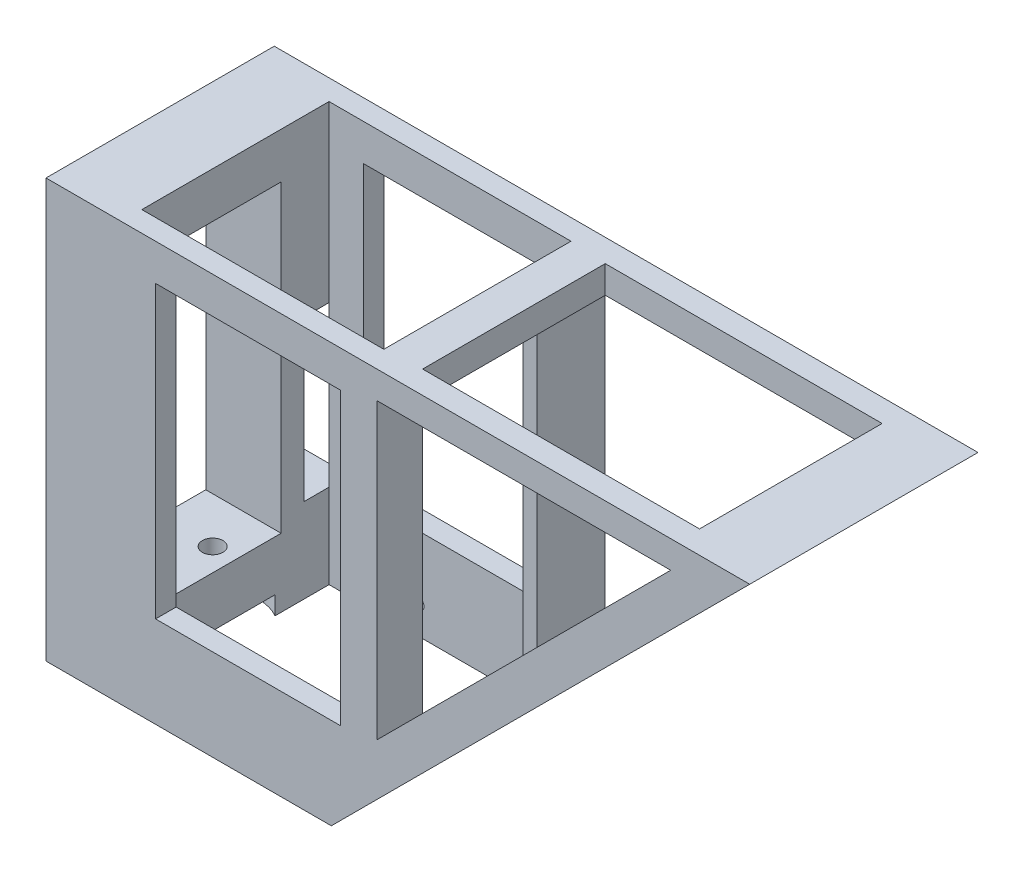
SolidWorks part; units mm, degrees
ref_plane "Plan de face" through (0, 0, 0) normal (0, 0, 1) x (1, 0, 0)
ref_plane "Plan de dessus" through (0, 0, 0) normal (0, 1, 0) x (1, 0, 0)
ref_plane "Plan de droite" through (0, 0, 0) normal (1, 0, 0) x (0, 0, -1)
sketch "Main-Sketch" plane through (0, 0, 0) normal (0, 0, 1) x (1, 0, 0)
  line L0 (0, 91.65) -> (154.15, 91.65)
  line L1 (154.15, 91.65) -> (62.5, 0)
  line L2 (62.5, 0) -> (0, 0)
  line L3 (0, 0) -> (0, 91.65)
  dimension "D1" = 62.5
  dimension "D2" = 154.15
  dimension "D3" = 135
extrude "Main-Extrusion" add sketch "Main-Sketch" along normal blind 50
ref_plane "Plan1" through (0, 0, 45) normal (0, 0, 1) x (1, 0, 0)
sketch "Fix-Bottom-Sheet-Sketch" plane through (0, 0, 0) normal (0, 0, -1) x (-1, 0, 0)
  line L0 (-62.5, 0) -> (-154.15, 91.65) construction
  circle A0 centre (-105.4994, 50.0705) radius 1.35
  circle A1 centre (-35.9453, 6.2286) radius 1.35
  dimension "D1" = 2.7
  dimension "D2" = 5
  dimension "D3" = 66
extrude "Fix-Bottom-Sheet-Extrusion" cut sketch "Fix-Bottom-Sheet-Sketch" against normal blind 10
sketch "Esquisse2" plane through (0, 0, 0) normal (0, -1, 0) x (-1, 0, 0)
  line L0 (0, -50) -> (0, 0) construction
  line L1 (-16.5, -45.5) -> (-69.5, -45.5)
  line L2 (-16.5, -45.5) -> (-16.5, -4.5)
  line L3 (-16.5, -4.5) -> (-69.5, -4.5)
  line L4 (-69.5, -45.5) -> (-69.5, -4.5)
  line L5 (0, -50) -> (-62.5, -50) construction
  point P4 (-16.5, -25)
  point P7 (0, -25)
  point P8 (0, 0)
  point P11 (-31.25, -50)
  point P12 (-69.5, -25)
  point P13 (-16.3275, -4.5)
  dimension "D1" = 41
  dimension "D2" = 16.5
  dimension "D3" = 53
extrude "Enlèv. mat.-Extru.2" cut sketch "Esquisse2" against normal through all
sketch "Esquisse3" plane through (0, 0, 50) normal (0, 0, 1) x (1, 0, 0)
  line L0 (72.5, 85.65) -> (72.5, 21.3137)
  line L1 (72.5, 21.3137) -> (136.8363, 85.65)
  line L2 (136.8363, 85.65) -> (72.5, 85.65)
  line L3 (62.5, 0) -> (154.15, 91.65) construction
  line L4 (154.15, 91.65) -> (0, 91.65) construction
  point P7 (76.6426, 83.65)
  dimension "D1" = 8
  dimension "D2" = 6
  dimension "D3" = 10
extrude "Enlèv. mat.-Extru.3" cut sketch "Esquisse3" against normal through all
sketch "Esquisse4" plane through (0, 0, 0) normal (0, 0, -1) x (-1, 0, 0)
  line L0 (0, 91.65) -> (0, 0) construction
  line L1 (0, 18.5) -> (-16.5, 18.5)
  line L2 (0, 18.5) -> (0, 53.5)
  line L3 (0, 53.5) -> (-16.5, 53.5)
  line L4 (-16.5, 18.5) -> (-16.5, 53.5)
  line L5 (0, 0) -> (-62.5, 0) construction
  dimension "D1" = 16.5
  dimension "D2" = 18.5
  dimension "D3" = 35
extrude "Enlèv. mat.-Extru.4" cut sketch "Esquisse4" against normal blind 10
sketch "Esquisse6" plane through (0, 0, 0) normal (0, -1, 0) x (1, 0, 0)
  line L0 (16.5, 45.5) -> (16.5, 4.5) construction
  line L1 (0, 50) -> (0, 0) construction
  circle A0 centre (11.5, 25) radius 10
  point P7 (0, 25)
  dimension "D1" = 20
  dimension "D2" = 5
extrude "Enlèv. mat.-Extru.6" cut sketch "Esquisse6" against normal blind 4
sketch "Esquisse7" plane through (0, 4, 0) normal (0, -1, 0) x (1, 0, 0)
  circle A0 centre (11.5, 25) radius 2.25
  circle A1 centre (11.5, 25) radius 10 construction
  dimension "D1" = 4.5
extrude "Enlèv. mat.-Extru.7" cut sketch "Esquisse7" against normal blind 15
ref_plane "Plan2" through (0, 15, 0) normal (0, -1, 0) x (1, 0, 0)
ref_plane "Plan3" through (0, 85.65, 0) normal (0, 1, 0) x (1, 0, 0)
sketch "Esquisse8" plane through (0, 85.65, 0) normal (0, 1, 0) x (-1, 0, 0)
  line L1 (-11.5, 40) -> (-5, 40)
  line L2 (-11.5, 40) -> (-11.5, 15)
  line L3 (-11.5, 15) -> (-5, 15)
  line L4 (-5, 40) -> (-5, 15)
  line L6 (-16.5, 45.5) -> (-16.5, 4.5) construction
  line L7 (0, 50) -> (0, 0) construction
  line L8 (-154.15, 0) -> (0, 0) construction
  line L9 (-154.15, 50) -> (0, 50) construction
  dimension "D1" = 5
  dimension "D2" = 5
  dimension "D3" = 15
  dimension "D4" = 10
extrude "Enlèv. mat.-Extru.8" cut sketch "Esquisse8" against normal up to surface (70.65 mm away) up to plane "Plan2"
sketch "Esquisse9" plane through (0, 0, 0) normal (-1, 0, 0) x (0, 0, 1)
  line L0 (-27.5, 15) -> (27.5, 15) construction
  line L1 (40, 81.65) -> (15, 81.65)
  line L2 (40, 81.65) -> (40, 15)
  line L3 (40, 15) -> (15, 15)
  line L4 (15, 81.65) -> (15, 15)
  line L5 (50, 91.65) -> (0, 91.65) construction
  line L6 (50, 91.65) -> (50, 0) construction
  line L7 (0, 91.65) -> (0, 53.5) construction
  point P4 (27.5, 15)
  dimension "D1" = 10
  dimension "D2" = 10
  dimension "D3" = 15
extrude "Enlèv. mat.-Extru.9" cut sketch "Esquisse9" against normal up to surface (72.5 mm away) up to face at (72.5, 53.4819, 25)
sketch "Esquisse10" plane through (0, 91.65, 0) normal (0, 1, 0) x (1, 0, 0)
  line L0 (154.15, -50) -> (0, -50) construction
  line L1 (138.15, -45) -> (77.5, -45)
  line L2 (138.15, -45) -> (138.15, -5)
  line L3 (138.15, -5) -> (77.5, -5)
  line L4 (77.5, -45) -> (77.5, -5)
  line L5 (154.15, 0) -> (0, 0) construction
  line L6 (69.5, -4.5) -> (69.5, -45.5) construction
  line L7 (154.15, -50) -> (154.15, 0) construction
  dimension "D1" = 5
  dimension "D2" = 5
  dimension "D3" = 8
  dimension "D4" = 16
extrude "Enlèv. mat.-Extru.10" cut sketch "Esquisse10" against normal up to next
sketch "Esquisse11" plane through (25.5931, -25.5931, 0) normal (-0.7071, 0.7071, 0) x (0.7071, 0.7071, 0)
  line L0 (173.8068, -50) -> (173.8068, 0) construction
  line L1 (153.8068, -45) -> (71.3363, -45)
  line L2 (153.8068, -45) -> (153.8068, -5)
  line L3 (153.8068, -5) -> (71.3363, -5)
  line L4 (71.3363, -45) -> (71.3363, -5)
  line L5 (66.3363, -50) -> (157.3216, -50) construction
  line L6 (66.3363, 0) -> (157.3216, 0) construction
  line L7 (66.3363, 0) -> (66.3363, -15) construction
  dimension "D1" = 20
  dimension "D2" = 5
  dimension "D3" = 5
  dimension "D4" = 5
extrude "Enlèv. mat.-Extru.11" cut sketch "Esquisse11" against normal blind 2
sketch "Esquisse12" plane through (0, 0, 0) normal (0, 0, -1) x (-1, 0, 0)
  line L0 (-154.15, 91.65) -> (0, 91.65) construction
  line L1 (-24, 83.65) -> (-64.5, 83.65)
  line L2 (-24, 83.65) -> (-24, 20)
  line L3 (-24, 20) -> (-64.5, 20)
  line L4 (-64.5, 20) -> (-64.5, 83.65)
  line L6 (0, 91.65) -> (0, 53.5) construction
  line L7 (0, 0) -> (-62.5, 0) construction
  line L9 (-72.5, 85.65) -> (-72.5, 21.3137) construction
  dimension "D1" = 8
  dimension "D3" = 24
  dimension "D4" = 20
  dimension "D5" = 8
extrude "Enlèv. mat.-Extru.12" cut sketch "Esquisse12" against normal through all
